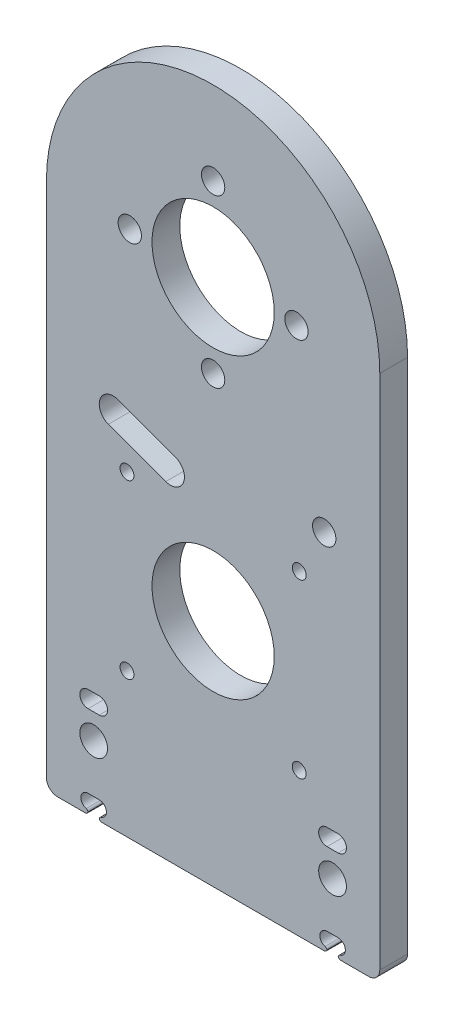
SolidWorks part; units mm, degrees
material "6061 Alloy"
ref_plane "Front Plane" through (0, 0, 0) normal (0, 0, 1) x (1, 0, 0)
ref_plane "Top Plane" through (0, 0, 0) normal (0, 1, 0) x (1, 0, 0)
ref_plane "Right Plane" through (0, 0, 0) normal (1, 0, 0) x (0, 0, -1)
sketch "Sketch1" plane through (0, 0, 0) normal (0, 0, 1) x (1, 0, 0)
  line L0 (20.5, -28) -> (22.5, -28) construction
  line L1 (-30, -46) -> (-22.5, -46)
  line L2 (-30, -46) -> (-30, 49)
  line L4 (30, -46) -> (30, 49)
  line L5 (0, 49) -> (0, -46) construction
  line L6 (22.5, -45.3) -> (22.5, -46)
  line L7 (-15.5, -20.1) -> (15.5, -20.1)
  line L8 (-15.5, -20.1) -> (-15.5, 10.9)
  line L9 (-15.5, 10.9) -> (15.5, 10.9)
  line L10 (15.5, -20.1) -> (15.5, 10.9)
  line L11 (0, 10.9) -> (0, -20.1) construction
  line L12 (-15.5, -4.6) -> (15.5, -4.6) construction
  line L13 (20.5, -26.5) -> (22.5, -26.5)
  line L14 (20.5, -29.5) -> (22.5, -29.5)
  line L15 (20.5, -44) -> (22.5, -44) construction
  line L16 (20.5, -42.7) -> (22.5, -42.7)
  line L18 (-20.5, -44) -> (-22.5, -44) construction
  line L19 (-20.5, -42.7) -> (-22.5, -42.7)
  line L21 (-20.5, -28) -> (-22.5, -28) construction
  line L22 (-20.5, -26.5) -> (-22.5, -26.5)
  line L23 (-20.5, -29.5) -> (-22.5, -29.5)
  line L29 (0, 64) -> (0, 34) construction
  line L30 (-15, 49) -> (15, 49) construction
  line L31 (20.5, -45.3) -> (20.5, -46)
  line L32 (-22.5, -45.3) -> (-22.5, -46)
  line L33 (-20.5, -45.3) -> (-20.5, -46)
  line L34 (-20.5, -46) -> (20.5, -46)
  line L35 (22.5, -46) -> (30, -46)
  line L36 (-7.6634, 15.2378) -> (-18, 19) construction
  line L37 (-8.5184, 12.8885) -> (-18.8551, 16.6508)
  line L38 (-6.8083, 17.587) -> (-17.1449, 21.3492)
  circle A1 centre (0, -4.6) radius 11
  circle A2 centre (15.5, 10.9) radius 1.25
  circle A3 centre (15.5, -20.1) radius 1.25
  circle A4 centre (-15.5, -20.1) radius 1.25
  circle A5 centre (-15.5, 10.9) radius 1.25
  circle A6 centre (0, 49) radius 11
  circle A7 centre (21.5, -34) radius 2.5
  arc A9 (20.5, -26.5) -> (20.5, -29.5) centre (20.5, -28) ccw
  arc A10 (22.5, -29.5) -> (22.5, -26.5) centre (22.5, -28) ccw
  arc A11 (20.5, -42.7) -> (20.5, -45.3) centre (20.5, -44) ccw
  arc A12 (22.5, -45.3) -> (22.5, -42.7) centre (22.5, -44) ccw
  arc A13 (-20.5, -42.7) -> (-20.5, -45.3) centre (-20.5, -44) cw
  arc A14 (-22.5, -45.3) -> (-22.5, -42.7) centre (-22.5, -44) cw
  circle A15 centre (-21.5, -34) radius 2.5
  arc A16 (-20.5, -26.5) -> (-20.5, -29.5) centre (-20.5, -28) cw
  arc A17 (-22.5, -29.5) -> (-22.5, -26.5) centre (-22.5, -28) cw
  circle A18 centre (0, 64) radius 2.1
  circle A19 centre (-15, 49) radius 2.1
  circle A20 centre (0, 34) radius 2.1
  circle A21 centre (15, 49) radius 2.1
  circle A22 centre (0, 49) radius 15 construction
  arc A23 (30, 49) -> (-30, 49) centre (0, 49) ccw
  circle A27 centre (20, 19.25) radius 2.1
  arc A28 (-8.5184, 12.8885) -> (-6.8083, 17.587) centre (-7.6634, 15.2378) ccw
  arc A29 (-17.1449, 21.3492) -> (-18.8551, 16.6508) centre (-18, 19) ccw
  point P0 (0, 0)
  point P21 (21.5, -28)
  point P27 (21.5, -44)
  point P33 (-21.5, -44)
  point P42 (-21.5, -28)
  point P49 (-12.8317, 17.1189)
  dimension "D4" = 22
  dimension "D5" = 2.5
  dimension "D8" = 22
  dimension "D12" = 5
  dimension "D16" = 1.5
  dimension "D18" = 1.3
  dimension "D21" = 4.2
  dimension "D19" = 30
  dimension "D6" = 2
  dimension "D14" = 2.5
  dimension "D1" = 60
  dimension "D3" = 95
  dimension "D7" = 15.5
  dimension "D9" = 53.6
  dimension "D10" = 18
  dimension "D11" = 8.5
  dimension "D13" = 10
  dimension "D15" = 2
  dimension "D17" = 2
  dimension "D20" = 11
  dimension "D22" = 12
  dimension "D23" = 15
  dimension "D24" = 70
  dimension "D25" = 20
extrude "Boss-Extrude1" add sketch "Sketch1" along normal mid plane 5 contours A21 A20 A19 L2 L1 L4 A14 L19 A13 A5 L9 A2 L10 A3 L7 A4 L8 A7 A10 L14 A9 L13 A12 A11 L16 A15 L23 A17 L22 A16 | A21 A6 A19 A20 | A21 A18 A19 A6 | A5 L8 A4 L7 A3 L10 A2 L9 A1 | A21 A19 A18 region at (0.1232, 14.5788, 0) region at (-14.3061, -18.9061, 0)
fillet "Fillet1" radius 0.5 8 edges at (-22.5, -46, 0) (-22.5, -45.3, 0) (-20.5, -46, 0) (-20.5, -45.3, 0) (20.5, -46, 0) (20.5, -45.3, 0) (22.5, -46, 0) (22.5, -45.3, 0)
fillet "Fillet2" radius 2 2 edges at (-30, -46, 0) (30, -46, 0)
